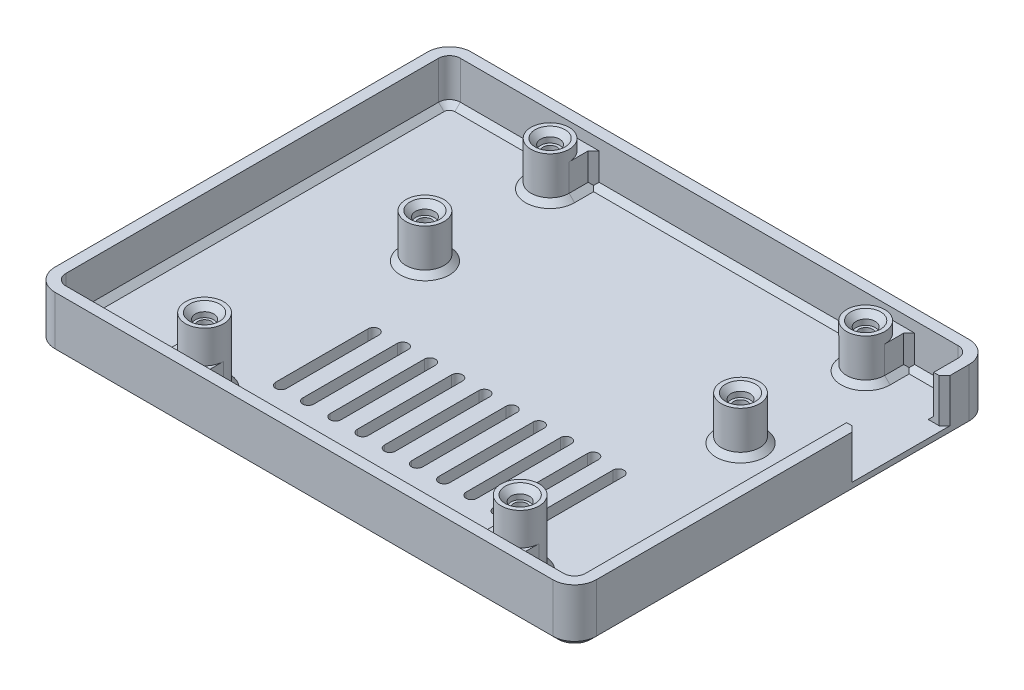
SolidWorks part; units mm, degrees
ref_plane "Front Plane" through (0, 0, 0) normal (0, 0, 1) x (1, 0, 0)
ref_plane "Top Plane" through (0, 0, 0) normal (0, 1, 0) x (1, 0, 0)
ref_plane "Right Plane" through (0, 0, 0) normal (1, 0, 0) x (0, 0, -1)
sketch "Sketch1" plane through (0, 0, 0) normal (0, 1, 0) x (1, 0, 0)
  line L0 (-65.617, -16.3721) -> (-0.617, -16.3721)
  line L1 (-62.117, 10.1279) -> (-4.117, 10.1279)
  line L2 (-62.117, 10.1279) -> (-62.117, -12.8721)
  line L3 (-65.617, 13.6279) -> (-0.617, 13.6279)
  line L4 (-65.617, 13.6279) -> (-65.617, -16.3721)
  line L5 (-62.117, -12.8721) -> (-4.117, -12.8721)
  line L6 (-0.617, 13.6279) -> (-0.617, -16.3721)
  line L7 (-4.117, 10.1279) -> (-4.117, -12.8721)
  line L8 (-24.217, 16.7282) -> (-24.217, 15.4455)
  line L9 (-11.617, 16.7282) -> (-11.617, 15.4455)
  dimension "D1" = 65
  dimension "D2" = 30
  dimension "D3" = 58
  dimension "D4" = 23
  dimension "D5" = 3.5
  dimension "D6" = 3.5
sketch "Sketch2" plane through (0, 0, 0) normal (0, 1, 0) x (1, 0, 0)
  line L1 (-0.617, 13.6279) -> (-0.617, -16.3721) construction
  line L2 (-65.617, 13.6279) -> (-65.617, -16.3721) construction
  line L7 (-85.117, 12.6279) -> (-85.117, -55.8721)
  line L10 (-83.117, -57.8721) -> (8.383, -57.8721)
  line L11 (-87.117, 12.6279) -> (-87.117, -55.8721)
  line L14 (10.383, 12.6279) -> (10.383, -55.8721)
  line L15 (-83.117, 14.6279) -> (8.383, 14.6279)
  line L16 (-83.117, -59.8721) -> (8.383, -59.8721)
  line L17 (12.383, 12.6279) -> (12.383, -55.8721)
  line L18 (-83.117, 16.6279) -> (8.383, 16.6279)
  arc A0 (-83.117, -57.8721) -> (-85.117, -55.8721) centre (-83.117, -55.8721) cw
  arc A1 (8.383, -57.8721) -> (10.383, -55.8721) centre (8.383, -55.8721) ccw
  arc A2 (10.383, 12.6279) -> (8.383, 14.6279) centre (8.383, 12.6279) ccw
  arc A3 (-83.117, 14.6279) -> (-85.117, 12.6279) centre (-83.117, 12.6279) ccw
  arc A4 (-83.117, -59.8721) -> (-87.117, -55.8721) centre (-83.117, -55.8721) cw
  arc A5 (8.383, -59.8721) -> (12.383, -55.8721) centre (8.383, -55.8721) ccw
  arc A6 (12.383, 12.6279) -> (8.383, 16.6279) centre (8.383, 12.6279) ccw
  arc A7 (-83.117, 16.6279) -> (-87.117, 12.6279) centre (-83.117, 12.6279) ccw
  dimension "D4" = 2
  dimension "D3" = 72.5
  dimension "D2" = 11
  dimension "D6" = 19.5
  dimension "D5" = 2
extrude "Boss-Extrude1" add sketch "Sketch2" along normal blind 10
extrude "Boss-Extrude2" add sketch "Sketch2<3>" along normal blind 2 contours L15 A3 L7 A0 L10 A1 L14 A2 region at (-37.367, 0, 21.6221)
sketch "Sketch2<3>" plane through (0, 0, 0) normal (0, 1, 0) x (1, 0, 0) same geometry as "Sketch2"
sketch "Sketch4" plane through (0, 2, 0) normal (0, 1, 0) x (1, 0, 0)
  line L0 (-58.617, 14.6279) -> (-58.617, 10.1279)
  line L1 (8.383, 14.6279) -> (-83.117, 14.6279) construction
  line L2 (-65.617, 14.6279) -> (-58.617, 14.6279)
  line L3 (-65.617, 10.1279) -> (-65.617, 14.6279)
  line L12 (-37.367, 14.6279) -> (-37.367, -57.8721) construction
  line L13 (-83.117, -57.8721) -> (8.383, -57.8721) construction
  line L14 (-0.617, 14.6279) -> (-0.617, 10.1279)
  line L15 (-7.617, 14.6279) -> (-0.617, 14.6279)
  line L16 (-7.617, 10.1279) -> (-7.617, 14.6279)
  circle A0 centre (-62.117, -12.8721) radius 3.5
  arc A1 (-58.617, 10.1279) -> (-65.617, 10.1279) centre (-62.117, 10.1279) cw
  arc A6 (-0.617, 10.1279) -> (-7.617, 10.1279) centre (-4.117, 10.1279) cw
  circle A7 centre (-4.117, -12.8721) radius 3.5
extrude "Boss-Extrude3" add sketch "Sketch4" along normal blind 8
sketch "Sketch7" plane through (0, 0, -16.6279) normal (0, 0, -1) x (-1, 0, 0)
  line L0 (11.617, 7.6) -> (11.617, 3.2) construction
  line L1 (7.617, 7.6) -> (15.617, 7.6)
  line L2 (7.617, 7.6) -> (7.617, 3.2)
  line L3 (7.617, 3.2) -> (15.617, 3.2)
  line L4 (15.617, 7.6) -> (15.617, 3.2)
  line L5 (-5.383, 7.6) -> (7.617, 7.6) construction
  line L6 (7.617, 7.6) -> (7.617, 2) construction
  dimension "D1" = 8
  dimension "D2" = 0
  dimension "D3" = 0
  dimension "D4" = 4.4
sketch "Sketch9" plane through (0, 2, 0) normal (0, 1, 0) x (1, 0, 0)
  line L1 (-83.117, -57.8721) -> (8.383, -57.8721) construction
  line L3 (-65.617, -57.8721) -> (-58.617, -57.8721)
  line L4 (-65.617, -53.3721) -> (-65.617, -57.8721)
  line L6 (-58.617, -57.8721) -> (-58.617, -53.3721)
  line L8 (-7.617, -53.3721) -> (-7.617, -57.8721)
  line L9 (-7.617, -57.8721) -> (-0.617, -57.8721)
  line L10 (-0.617, -57.8721) -> (-0.617, -53.3721)
  arc A0 (-0.617, -53.3721) -> (-7.617, -53.3721) centre (-4.117, -53.3721) ccw
  arc A1 (-58.617, -53.3721) -> (-65.617, -53.3721) centre (-62.117, -53.3721) ccw
extrude "Boss-Extrude4" add sketch "Sketch9" along normal offset from surface (12 mm away) 4 up to face at (-37.367, 10, 21.6221) offset beyond the face yes
chamfer "Chamfer3" distance 1 angle 45 8 edges at (12.383, 0, 21.6221) (11.2114, 0, -15.4563) (11.2114, 0, 58.7006) (-37.367, 0, -16.6279) (-37.367, 0, 59.8721) (-85.9454, 0, -15.4563) (-85.9454, 0, 58.7006) (-87.117, 0, 21.6221)
sketch "Sketch12" plane through (0, 10, 0) normal (0, 1, 0) x (1, 0, 0)
  line L0 (-65.617, 10.1279) -> (-65.617, 14.6279)
  line L1 (-58.617, 14.6279) -> (-58.617, 10.1279)
  line L2 (-65.617, 14.6279) -> (-58.617, 14.6279)
  line L4 (-65.617, -53.3721) -> (-65.617, -57.8721)
  line L5 (-58.617, -57.8721) -> (-58.617, -53.3721)
  line L6 (-65.617, -57.8721) -> (-58.617, -57.8721)
  line L8 (-7.617, -53.3721) -> (-7.617, -57.8721)
  line L9 (-7.617, -57.8721) -> (-0.617, -57.8721)
  line L10 (-0.617, -57.8721) -> (-0.617, -53.3721)
  line L12 (-7.617, 10.1279) -> (-7.617, 14.6279)
  line L13 (-7.617, 14.6279) -> (-0.617, 14.6279)
  line L14 (-0.617, 14.6279) -> (-0.617, 10.1279)
  arc A0 (-58.617, 10.1279) -> (-65.617, 10.1279) centre (-62.117, 10.1279) ccw
  arc A2 (-65.617, -53.3721) -> (-58.617, -53.3721) centre (-62.117, -53.3721) ccw
  arc A4 (-7.617, -53.3721) -> (-0.617, -53.3721) centre (-4.117, -53.3721) ccw
  arc A6 (-0.617, 10.1279) -> (-7.617, 10.1279) centre (-4.117, 10.1279) ccw
extrude "Cut-Extrude2" cut sketch "Sketch12" against normal blind 2 and the other way blind 4
chamfer "Chamfer4" distance 1 angle 45 8 edges at (-0.617, 5, -14.6279) (-7.617, 5, -14.6279) (-0.617, 5, 57.8721) (-7.617, 5, 57.8721) (-58.617, 5, 57.8721) (-65.617, 5, 57.8721) (-58.617, 5, -14.6279) (-65.617, 5, -14.6279)
chamfer "Chamfer5" distance 1 angle 45 26 edges at (-4.117, 2, 9.3721) (10.383, 2, 21.6221) (4.383, 2, -14.6279) (9.7972, 2, -14.0421) (-7.617, 2, -11.8779) (-0.617, 2, -11.8779) (-4.117, 2, -6.6279) (-33.117, 2, -14.6279) (-85.117, 2, 21.6221) (4.383, 2, 57.8721) (9.7972, 2, 57.2864) (-0.617, 2, 55.1221) (-7.617, 2, 55.1221) (-4.117, 2, 49.8721) (-74.867, 2, -14.6279) (-84.5312, 2, -14.0421) (-33.117, 2, 57.8721) (-74.867, 2, 57.8721) (-84.5312, 2, 57.2864) (-65.617, 2, -11.8779) (-58.617, 2, -11.8779) (-62.117, 2, -6.6279) (-62.117, 2, 9.3721) (-58.617, 2, 55.1221) (-65.617, 2, 55.1221) (-62.117, 2, 49.8721)
hole_wizard "Ø2.5 (2.5) Diameter Hole1" positions "Sketch14" profile "Sketch13" hole size "Ø2.5" standard "ANSI Metric"
sketch "Sketch14" plane through (0, 10, 0) normal (0, 1, 0) x (1, 0, 0)
  point P0 (-62.117, 10.1279)
  point P4 (-4.117, 10.1279)
  point P8 (-62.117, -12.8721)
  point P12 (-4.117, -12.8721)
sketch "Sketch13" plane through (-62.117, 10, -10.1279) normal (1, 0, 0) x (0, 0, 1)
  line L0 (0, 0) -> (0, 8)
  line L1 (0, 8) -> (1.25, 8)
  line L2 (1.25, 8) -> (1.25, 1.5)
  line L3 (1.25, 1.5) -> (2.75, 0)
  line L5 (2.75, 0) -> (0, 0)
  line L6 (-1.25, 1.5) -> (-2.75, 0) construction
  line L10 (0, 8) -> (-1.25, 8) construction
  line L11 (0, -6.35) -> (0, 107.95) construction
  dimension "Hole Dia." = 2.5
  dimension "Hole Depth" = 8
  dimension "Near C'Sink Dia." = 5.5
  dimension "Near C'Sink Angle" = 90
  dimension "Drill Angle" = 180
hole_wizard "Ø3.5 (3.5) Diameter Hole1" positions "Sketch16" profile "Sketch15" hole size "Ø3.5" standard "ANSI Metric"
sketch "Sketch16" plane through (0, 10, 0) normal (0, 1, 0) x (1, 0, 0)
  point P0 (-62.117, 10.1279)
  point P4 (-4.117, 10.1279)
  point P8 (-62.117, -12.8721)
  point P12 (-4.117, -12.8721)
sketch "Sketch15" plane through (-62.117, 10, -10.1279) normal (1, 0, 0) x (0, 0, 1)
  line L0 (0, 0) -> (0, 2)
  line L1 (0, 2) -> (1.75, 2)
  line L2 (1.75, 2) -> (1.75, 0)
  line L5 (1.75, 0) -> (0, 0)
  line L10 (0, 2) -> (-1.75, 2) construction
  line L11 (0, -6.35) -> (0, 107.95) construction
  dimension "Hole Dia." = 3.5
  dimension "Hole Depth" = 2
  dimension "Drill Angle" = 180
hole_wizard "Ø2.5 (2.5) Diameter Hole2" positions "Sketch18" profile "Sketch17" hole size "Ø2.5" standard "ANSI Metric"
sketch "Sketch18" plane through (0, 14, 0) normal (0, 1, 0) x (1, 0, 0)
  point P0 (-62.117, -53.3721)
  point P7 (-4.117, -53.3721)
sketch "Sketch17" plane through (-62.117, 14, 53.3721) normal (1, 0, 0) x (0, 0, 1)
  line L0 (0, 0) -> (0, 12)
  line L1 (0, 12) -> (1.25, 12)
  line L2 (1.25, 12) -> (1.25, 1.5)
  line L3 (1.25, 1.5) -> (2.75, 0)
  line L5 (2.75, 0) -> (0, 0)
  line L6 (-1.25, 1.5) -> (-2.75, 0) construction
  line L10 (0, 12) -> (-1.25, 12) construction
  line L11 (0, -6.35) -> (0, 107.95) construction
  dimension "Hole Dia." = 2.5
  dimension "Hole Depth" = 12
  dimension "Near C'Sink Dia." = 5.5
  dimension "Near C'Sink Angle" = 90
  dimension "Drill Angle" = 180
hole_wizard "Ø3.4 (3.4) Diameter Hole1" positions "Sketch20" profile "Sketch19" hole size "Ø3.4" standard "ANSI Metric"
sketch "Sketch20" plane through (0, 14, 0) normal (0, 1, 0) x (1, 0, 0)
  point P0 (-62.117, -53.3721)
  point P7 (-4.117, -53.3721)
sketch "Sketch19" plane through (-62.117, 14, 53.3721) normal (1, 0, 0) x (0, 0, 1)
  line L0 (0, 0) -> (0, 2)
  line L1 (0, 2) -> (1.7, 2)
  line L2 (1.7, 2) -> (1.7, 0)
  line L5 (1.7, 0) -> (0, 0)
  line L10 (0, 2) -> (-1.7, 2) construction
  line L11 (0, -6.35) -> (0, 107.95) construction
  dimension "Hole Dia." = 3.4
  dimension "Hole Depth" = 2
  dimension "Drill Angle" = 180
sketch "Sketch21" plane through (12.383, 0, 0) normal (1, 0, 0) x (0, 0, -1)
  line L0 (-55.8721, 10) -> (12.6279, 10) construction
  line L1 (-7.8721, 10) -> (8.1279, 10)
  line L2 (-7.8721, 10) -> (-7.8721, 2)
  line L3 (-7.8721, 2) -> (8.1279, 2)
  line L4 (8.1279, 10) -> (8.1279, 2)
  line L5 (0.1279, 10) -> (0.1279, 2) construction
  dimension "D1" = 8
  dimension "D2" = 16
  dimension "D3" = 10
extrude "Cut-Extrude3" cut sketch "Sketch21" against normal up to next
chamfer "Chamfer9" distance 1 angle 45 2 edges at (12.383, 6, 7.8721) (12.383, 6, -8.1279)
sketch "Sketch22" plane through (-87.117, 0, 0) normal (-1, 0, 0) x (0, 0, 1)
  line L0 (-12.6279, 10) -> (55.8721, 10) construction
  line L1 (-5.6279, 10) -> (3.3721, 10)
  line L2 (-5.6279, 10) -> (-5.6279, 4)
  line L3 (-5.6279, 4) -> (3.3721, 4)
  line L4 (3.3721, 10) -> (3.3721, 4)
  line L5 (-1.1279, 10) -> (-1.1279, 4) construction
  dimension "D1" = 9
  dimension "D2" = 6
  dimension "D3" = 9
extrude "Cut-Extrude4" [suppressed] cut sketch "Sketch22" against normal up to next
chamfer "Chamfer10" [suppressed] distance 1 angle 45
sketch "Sketch23" plane through (0, 2, 0) normal (0, 1, 0) x (1, 0, 0)
  line L0 (-55.5268, -28.9025) -> (-55.5268, -45.9025) construction
  line L1 (-54.5268, -28.9025) -> (-54.5268, -45.9025)
  line L2 (-56.5268, -28.9025) -> (-56.5268, -45.9025)
  line L3 (-50.5268, -28.5517) -> (-50.5268, -45.9025) construction
  line L4 (-49.5268, -28.5517) -> (-49.5268, -45.9025)
  line L5 (-51.5268, -28.5517) -> (-51.5268, -45.9025)
  line L6 (-45.5268, -28.5526) -> (-45.5268, -45.9025) construction
  line L7 (-44.5268, -28.5526) -> (-44.5268, -45.9025)
  line L8 (-46.5268, -28.5526) -> (-46.5268, -45.9025)
  line L9 (-40.5268, -28.5536) -> (-40.5268, -45.9025) construction
  line L10 (-39.5268, -28.5536) -> (-39.5268, -45.9025)
  line L11 (-41.5268, -28.5536) -> (-41.5268, -45.9025)
  line L12 (-35.5268, -28.5546) -> (-35.5268, -45.9025) construction
  line L13 (-34.5268, -28.5546) -> (-34.5268, -45.9025)
  line L14 (-36.5268, -28.5546) -> (-36.5268, -45.9025)
  line L15 (-30.5268, -28.5556) -> (-30.5268, -45.9025) construction
  line L16 (-29.5268, -28.5556) -> (-29.5268, -45.9025)
  line L17 (-31.5268, -28.5556) -> (-31.5268, -45.9025)
  line L18 (-25.5268, -28.5565) -> (-25.5268, -45.9025) construction
  line L19 (-24.5268, -28.5565) -> (-24.5268, -45.9025)
  line L20 (-26.5268, -28.5565) -> (-26.5268, -45.9025)
  line L21 (-20.5268, -28.5575) -> (-20.5268, -45.9025) construction
  line L22 (-19.5268, -28.5575) -> (-19.5268, -45.9025)
  line L23 (-21.5268, -28.5575) -> (-21.5268, -45.9025)
  line L24 (-15.5268, -28.5585) -> (-15.5268, -45.9025) construction
  line L25 (-14.5268, -28.5585) -> (-14.5268, -45.9025)
  line L26 (-16.5268, -28.5585) -> (-16.5268, -45.9025)
  line L27 (-10.5268, -28.9025) -> (-10.5268, -45.9025) construction
  line L28 (-9.5268, -28.9025) -> (-9.5268, -45.9025)
  line L29 (-11.5268, -28.9025) -> (-11.5268, -45.9025)
  arc A0 (-54.5268, -28.9025) -> (-56.5268, -28.9025) centre (-55.5268, -28.9025) ccw
  arc A1 (-56.5268, -45.9025) -> (-54.5268, -45.9025) centre (-55.5268, -45.9025) ccw
  arc A2 (-49.5268, -28.5517) -> (-51.5268, -28.5517) centre (-50.5268, -28.5517) ccw
  arc A3 (-51.5268, -45.9025) -> (-49.5268, -45.9025) centre (-50.5268, -45.9025) ccw
  arc A4 (-44.5268, -28.5526) -> (-46.5268, -28.5526) centre (-45.5268, -28.5526) ccw
  arc A5 (-46.5268, -45.9025) -> (-44.5268, -45.9025) centre (-45.5268, -45.9025) ccw
  arc A6 (-39.5268, -28.5536) -> (-41.5268, -28.5536) centre (-40.5268, -28.5536) ccw
  arc A7 (-41.5268, -45.9025) -> (-39.5268, -45.9025) centre (-40.5268, -45.9025) ccw
  arc A8 (-34.5268, -28.5546) -> (-36.5268, -28.5546) centre (-35.5268, -28.5546) ccw
  arc A9 (-36.5268, -45.9025) -> (-34.5268, -45.9025) centre (-35.5268, -45.9025) ccw
  arc A10 (-29.5268, -28.5556) -> (-31.5268, -28.5556) centre (-30.5268, -28.5556) ccw
  arc A11 (-31.5268, -45.9025) -> (-29.5268, -45.9025) centre (-30.5268, -45.9025) ccw
  arc A12 (-24.5268, -28.5565) -> (-26.5268, -28.5565) centre (-25.5268, -28.5565) ccw
  arc A13 (-26.5268, -45.9025) -> (-24.5268, -45.9025) centre (-25.5268, -45.9025) ccw
  arc A14 (-19.5268, -28.5575) -> (-21.5268, -28.5575) centre (-20.5268, -28.5575) ccw
  arc A15 (-21.5268, -45.9025) -> (-19.5268, -45.9025) centre (-20.5268, -45.9025) ccw
  arc A16 (-14.5268, -28.5585) -> (-16.5268, -28.5585) centre (-15.5268, -28.5585) ccw
  arc A17 (-16.5268, -45.9025) -> (-14.5268, -45.9025) centre (-15.5268, -45.9025) ccw
  arc A18 (-9.5268, -28.9025) -> (-11.5268, -28.9025) centre (-10.5268, -28.9025) ccw
  arc A19 (-11.5268, -45.9025) -> (-9.5268, -45.9025) centre (-10.5268, -45.9025) ccw
  point P2 (-55.5268, -37.4025)
  point P9 (-50.5268, -37.2271)
  point P16 (-45.5268, -37.2276)
  point P23 (-40.5268, -37.2281)
  point P30 (-35.5268, -37.2286)
  point P37 (-30.5268, -37.229)
  point P44 (-25.5268, -37.2295)
  point P51 (-20.5268, -37.23)
  point P58 (-15.5268, -37.2305)
  point P65 (-10.5268, -37.4025)
  dimension "D1" = 2
  dimension "D2" = 17
extrude "Cut-Extrude5" cut sketch "Sketch23" against normal up to next
